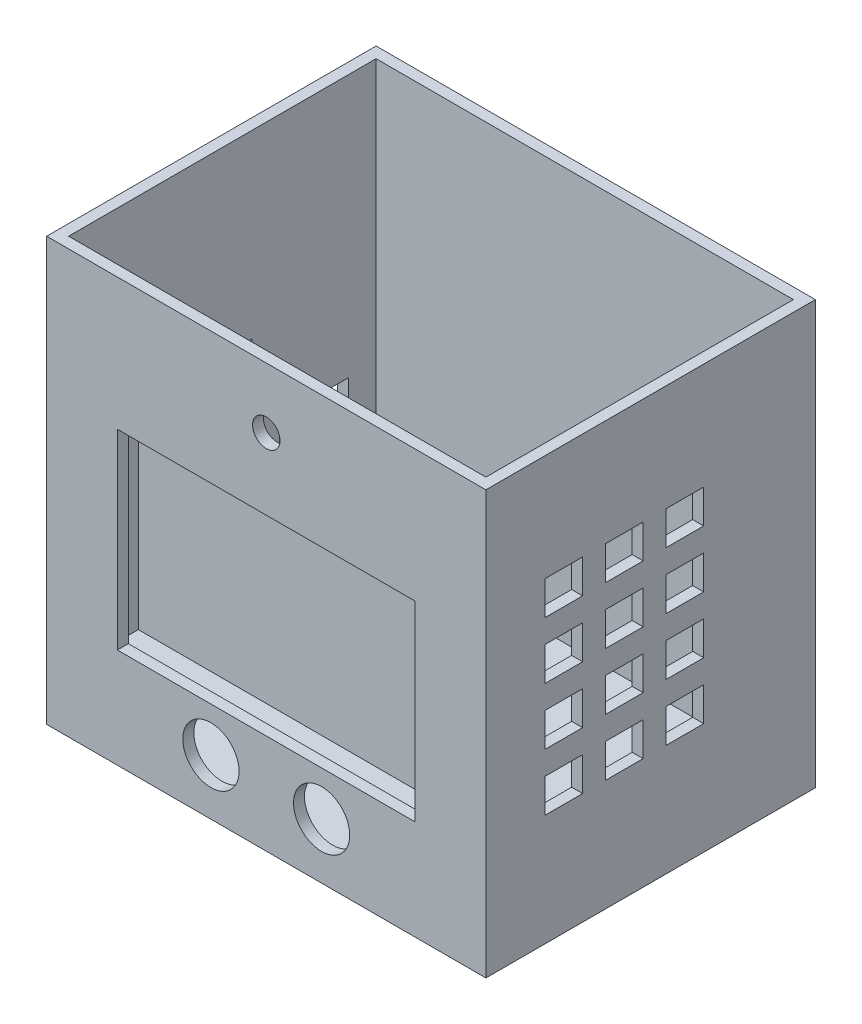
SolidWorks part; units mm, degrees
ref_plane "Front Plane" through (0, 0, 0) normal (0, 0, 1) x (1, 0, 0)
ref_plane "Top Plane" through (0, 0, 0) normal (0, 1, 0) x (1, 0, 0)
ref_plane "Right Plane" through (0, 0, 0) normal (1, 0, 0) x (0, 0, -1)
sketch "Sketch1" plane through (0, 0, 0) normal (0, 1, 0) x (1, 0, 0)
  line L1 (-50.8, 38.1) -> (50.8, 38.1)
  line L2 (-50.8, 38.1) -> (-50.8, -38.1)
  line L3 (-50.8, -38.1) -> (50.8, -38.1)
  line L4 (50.8, 38.1) -> (50.8, -38.1)
  line L5 (-50.8, 38.1) -> (50.8, -38.1) construction
  line L6 (-50.8, -38.1) -> (50.8, 38.1) construction
  point P0 (0, 0)
  dimension "D1" = 76.2
  dimension "D2" = 101.6
extrude "Boss-Extrude1" add sketch "Sketch1" along normal blind 97.79
ref_plane "Plane3" through (0, 0, 38.1) normal (0, 0, 1) x (1, 0, 0)
sketch "Sketch5" plane through (0, 0, 38.1) normal (0, 0, 1) x (1, 0, 0)
  line L0 (-50.8, 48.895) -> (50.8, 48.895) construction
  line L1 (-50.8, 97.79) -> (-50.8, 0) construction
  line L2 (50.8, 97.79) -> (50.8, 0) construction
  line L3 (0, 97.79) -> (0, 0) construction
  line L4 (-50.8, 97.79) -> (50.8, 97.79) construction
  line L6 (-34.4446, 67.31) -> (34.4446, 67.31)
  line L7 (-34.4446, 67.31) -> (-34.4446, 23.0772)
  line L8 (-34.4446, 23.0772) -> (34.4446, 23.0772)
  line L9 (34.4446, 67.31) -> (34.4446, 23.0772)
  line L10 (-34.4446, 67.31) -> (34.4446, 23.0772) construction
  line L11 (-34.4446, 23.0772) -> (34.4446, 67.31) construction
  point P11 (0, 48.895)
  point P12 (0, 45.1936)
  dimension "D1" = 68.8893
  dimension "D2" = 30.48
  dimension "D3" = 44.2328
extrude "Cut-Extrude3" cut sketch "Sketch5" against normal blind 2.54
shell "Shell1" thickness 2.54 removed face at (0, 45.1936, 35.56) removed face at (0, 97.79, 0)
ref_plane "Plane5" through (0, 0, 35.56) normal (0, 0, -1) x (-1, 0, 0)
sketch "Sketch7" plane through (0, 0, 35.56) normal (0, 0, -1) x (-1, 0, 0)
  line L0 (34.4446, 45.1936) -> (-34.4446, 45.1936) construction
  line L1 (34.4446, 67.31) -> (34.4446, 23.0772) construction
  line L2 (-34.4446, 23.0772) -> (-34.4446, 67.31) construction
  line L3 (0, 67.31) -> (0, 23.0772) construction
  line L4 (-34.4446, 67.31) -> (34.4446, 67.31) construction
  line L5 (34.4446, 23.0772) -> (-34.4446, 23.0772) construction
  line L6 (-50.8, 97.79) -> (50.8, 97.79) construction
  line L7 (37.592, 67.31) -> (-37.592, 67.31)
  line L8 (37.592, 67.31) -> (37.592, 21.59)
  line L9 (37.592, 21.59) -> (-37.592, 21.59)
  line L10 (-37.592, 67.31) -> (-37.592, 21.59)
  line L11 (37.592, 67.31) -> (-37.592, 21.59) construction
  line L12 (37.592, 21.59) -> (-37.592, 67.31) construction
  point P12 (0, 45.1936)
  point P13 (0, 44.45)
  dimension "D1" = 30.48
  dimension "D2" = 75.184
  dimension "D3" = 45.72
extrude "Boss-Extrude9" add sketch "Sketch7" along normal blind 5.461 separate body
shell "Shell3" thickness 2.54 removed face at (0, 44.45, 35.56) removed face at (0, 67.31, 32.8295) outward yes
sketch "Sketch8" plane through (0, 67.31, 0) normal (0, 1, 0) x (1, 0, 0)
  line L0 (37.592, -30.099) -> (37.592, -35.56) construction
  line L1 (37.592, -33.0069) -> (3.302, -33.0069)
  line L2 (37.592, -33.0069) -> (37.592, -22.7768)
  line L3 (37.592, -22.7768) -> (3.302, -22.7768)
  line L4 (3.302, -33.0069) -> (3.302, -22.7768)
  dimension "D1" = 34.29
extrude "Cut-Extrude4" cut sketch "Sketch8" against normal blind 6.35
ref_plane "Plane6" through (-50.8, 0, 0) normal (1, 0, 0) x (0, 0, -1)
sketch "Sketch9" plane through (-50.8, 0, 53.34) normal (-1, 0, 0) x (0, 0, 1)
  line L1 (-82.55, 4.572) -> (-66.548, 4.572)
  line L2 (-82.55, 4.572) -> (-82.55, 19.3675)
  line L3 (-82.55, 19.3675) -> (-66.548, 19.3675)
  line L4 (-66.548, 4.572) -> (-66.548, 19.3675)
  line L8 (-91.44, 97.79) -> (-91.44, 0) construction
  line L9 (-91.44, 0) -> (-15.24, 0) construction
  line L11 (-82.55, 22.2885) -> (-66.548, 22.2885)
  line L12 (-82.55, 22.2885) -> (-82.55, 37.084)
  line L13 (-82.55, 37.084) -> (-66.548, 37.084)
  line L14 (-66.548, 22.2885) -> (-66.548, 37.084)
  dimension "D1" = 8.89
  dimension "D2" = 16.002
  dimension "D3" = 14.7955
  dimension "D4" = 4.572
  dimension "D5" = 2.921
  dimension "D6" = 14.7955
extrude "Cut-Extrude6" cut sketch "Sketch9" against normal blind 2.54
sketch "Sketch12" plane through (-50.8, 0, 0) normal (-1, 0, 0) x (0, 0, 1)
  line L1 (-6.858, 56.0036) -> (21.082, 56.0036)
  line L2 (-6.858, 56.0036) -> (-6.858, 12.8236)
  line L3 (-6.858, 12.8236) -> (21.082, 12.8236)
  line L4 (21.082, 56.0036) -> (21.082, 12.8236)
  line L5 (-6.858, 56.0036) -> (21.082, 12.8236) construction
  line L6 (-6.858, 12.8236) -> (21.082, 56.0036) construction
  line L7 (-13.208, 4.572) -> (-13.208, 19.3675) construction
  line L8 (-38.1, 0) -> (38.1, 0) construction
  point P0 (7.112, 34.4136)
  dimension "D1" = 27.94
  dimension "D2" = 43.18
  dimension "D3" = 6.35
  dimension "D4" = 12.8236
extrude "Cut-Extrude7" cut sketch "Sketch12" against normal blind 2.54 contours L2 L1 L4 L3
sketch "Sketch13" plane through (0, 2.54, 0) normal (0, 1, 0) x (1, 0, 0)
  line L0 (-48.26, 0) -> (48.26, 0) construction
  line L1 (-48.26, 35.56) -> (-48.26, -35.56) construction
  line L2 (48.26, -35.56) -> (48.26, 35.56) construction
  line L3 (0, 35.56) -> (0, -35.56) construction
  line L4 (48.26, 35.56) -> (-48.26, 35.56) construction
  line L5 (52.3875, -35.56) -> (-52.3875, -35.56) construction
  line L7 (-15.76, 6.35) -> (7.1, 6.35)
  line L8 (-15.76, 6.35) -> (-15.76, -6.35)
  line L9 (-15.76, -6.35) -> (7.1, -6.35)
  line L10 (7.1, 6.35) -> (7.1, -6.35)
  line L11 (-15.76, 6.35) -> (7.1, -6.35) construction
  line L12 (-15.76, -6.35) -> (7.1, 6.35) construction
  point P13 (-4.33, 0)
  dimension "D1" = 12.7
  dimension "D2" = 22.86
  dimension "D3" = 4.33
extrude "Cut-Extrude8" cut sketch "Sketch13" against normal blind 2.54
sketch "Sketch14" plane through (0, 0, 38.1) normal (0, 0, 1) x (1, 0, 0)
  line L0 (0, 0) -> (0, 23.0772) construction
  line L1 (-34.4446, 23.0772) -> (34.4446, 23.0772) construction
  line L2 (-12.8, 12.84) -> (12.8, 12.84) construction
  line L3 (-50.8, 0) -> (50.8, 0) construction
  circle A0 centre (-12.8, 12.84) radius 6.5
  circle A1 centre (12.8, 12.84) radius 6.5
  point P8 (0, 11.5386)
  dimension "D2" = 13
  dimension "D3" = 12.84
  dimension "D1" = 25.6
extrude "Cut-Extrude10" cut sketch "Sketch14" against normal blind 12.7
sketch "Sketch16" plane through (0, 0, 38.1) normal (0, 0, 1) x (1, 0, 0)
  line L0 (0, 97.79) -> (0, 67.31) construction
  line L1 (-50.8, 97.79) -> (50.8, 97.79) construction
  line L2 (34.4446, 67.31) -> (-34.4446, 67.31) construction
  circle A0 centre (0, 83.82) radius 3.175
  point P6 (0, 83.82)
  dimension "D1" = 6.35
  dimension "D2" = 13.97
extrude "Cut-Extrude11" cut sketch "Sketch16" against normal blind 2.54
ref_plane "Plane7" through (50.8, 0, 0) normal (1, 0, 0) x (0, 0, -1)
sketch "Sketch17" plane through (50.8, 0, 0) normal (1, 0, 0) x (0, 0, -1)
  line L1 (-24.4499, 73.1623) -> (-15.7299, 73.1623)
  line L2 (-24.4499, 73.1623) -> (-24.4499, 65.3623)
  line L3 (-24.4499, 65.3623) -> (-15.7299, 65.3623)
  line L4 (-15.7299, 73.1623) -> (-15.7299, 65.3623)
  dimension "D1" = 7.8
  dimension "D2" = 8.7201
extrude "Cut-Extrude12" cut sketch "Sketch17" against normal blind 2.54
pattern_linear "LPattern1" count 3 spacing 14 along (0, 0, -1) count 4 spacing 13.2 along (0, -1, 0) of "Cut-Extrude12"
